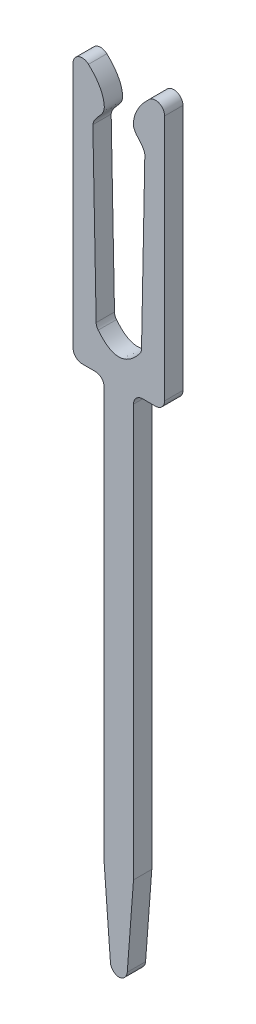
SolidWorks part; units mm, degrees
material "1060 Alloy"
ref_plane "Front Plane" through (0, 0, 0) normal (0, 0, 1) x (1, 0, 0)
ref_plane "Top Plane" through (0, 0, 0) normal (0, 1, 0) x (1, 0, 0)
ref_plane "Right Plane" through (0, 0, 0) normal (1, 0, 0) x (0, 0, -1)
sketch "Sketch1" plane through (0, 0, 0) normal (0, 0, 1) x (1, 0, 0)
  line L0 (-0.32, -7.7332) -> (-0.32, 1.2668)
  line L1 (-0.1839, -9.5482) -> (-0.32, -7.7332)
  line L2 (-0.5677, 6.1083) -> (-0.4952, 2.4017)
  line L3 (-1, 1.6668) -> (-1, 7.0572)
  line L4 (0.1839, -9.5482) -> (0.32, -7.7332)
  line L5 (0.32, -7.7332) -> (0.32, 1.2668)
  line L6 (0.52, 1.4668) -> (0.8, 1.4668)
  line L7 (1, 1.6668) -> (1, 7.0572)
  line L8 (0.5677, 6.1083) -> (0.4952, 2.4017)
  line L9 (-0.52, 1.4668) -> (-0.8, 1.4668)
  line L10 (0, 2) -> (0, -9.7326) construction
  arc A0 (0, -9.7326) -> (-0.1839, -9.5482) centre (0.0156, -9.5332) cw
  arc A1 (-0.4952, 2.4017) -> (-0.4511, 2.2802) centre (-0.2953, 2.4056) ccw
  arc A2 (-1, 7.0572) -> (-0.663, 7.2029) centre (-0.8, 7.0572) cw
  arc A3 (-0.8, 1.4668) -> (-1, 1.6668) centre (-0.8, 1.6668) cw
  arc A4 (0, -9.7326) -> (0.1839, -9.5482) centre (-0.0156, -9.5332) ccw
  arc A5 (0.32, 1.2668) -> (0.52, 1.4668) centre (0.52, 1.2668) cw
  arc A6 (0.8, 1.4668) -> (1, 1.6668) centre (0.8, 1.6668) ccw
  arc A7 (1, 7.0572) -> (0.663, 7.2029) centre (0.8, 7.0572) ccw
  arc A8 (0.4952, 2.4017) -> (0.4511, 2.2802) centre (0.2953, 2.4056) cw
  arc A9 (-0.32, 1.2668) -> (-0.52, 1.4668) centre (-0.52, 1.2668) ccw
  spline S0 degree 3 poles (0.663, 7.2029) (0.4876, 7.0381) (0.3262, 6.8162) (0.3107, 6.3882) (0.5485, 6.276) (0.5677, 6.1083) knots 0.253308 0.253308 0.253308 0.253308 0.663172 0.707067 1 1 1 1
  spline S1 degree 2 poles (-0.4511, 2.2802) (0, 1.7198) (0.4511, 2.2802) knots 0.043405 0.043405 0.043405 0.956595 0.956595 0.956595
  spline S2 degree 3 poles (-0.663, 7.2029) (-0.4876, 7.0381) (-0.3262, 6.8162) (-0.3107, 6.3882) (-0.5485, 6.276) (-0.5677, 6.1083) knots 0.253308 0.253308 0.253308 0.253308 0.663172 0.707067 1 1 1 1
  dimension "D2" = 0.2
  dimension "D7" = 0.2
  dimension "D8" = 0.68
  dimension "D10" = 0.2
  dimension "D13" = 0.2
  dimension "D3" = 0.1839
  dimension "D4" = 1.815
  dimension "D5" = 2
  dimension "D6" = 9
  dimension "D9" = 5.3904
  dimension "D11" = 0.8134
  dimension "D12" = 0.1215
  dimension "D14" = 0.4323
  dimension "D15" = 0.337
  dimension "D16" = 0.9489
  dimension "D17" = 0.5048
  dimension "D18" = 0.64
extrude "Boss-Extrude1" add sketch "Sketch1" against normal mid plane 0.4
ref_axis "Axis1" through (0, 2, 0) along (0, -1, 0)
